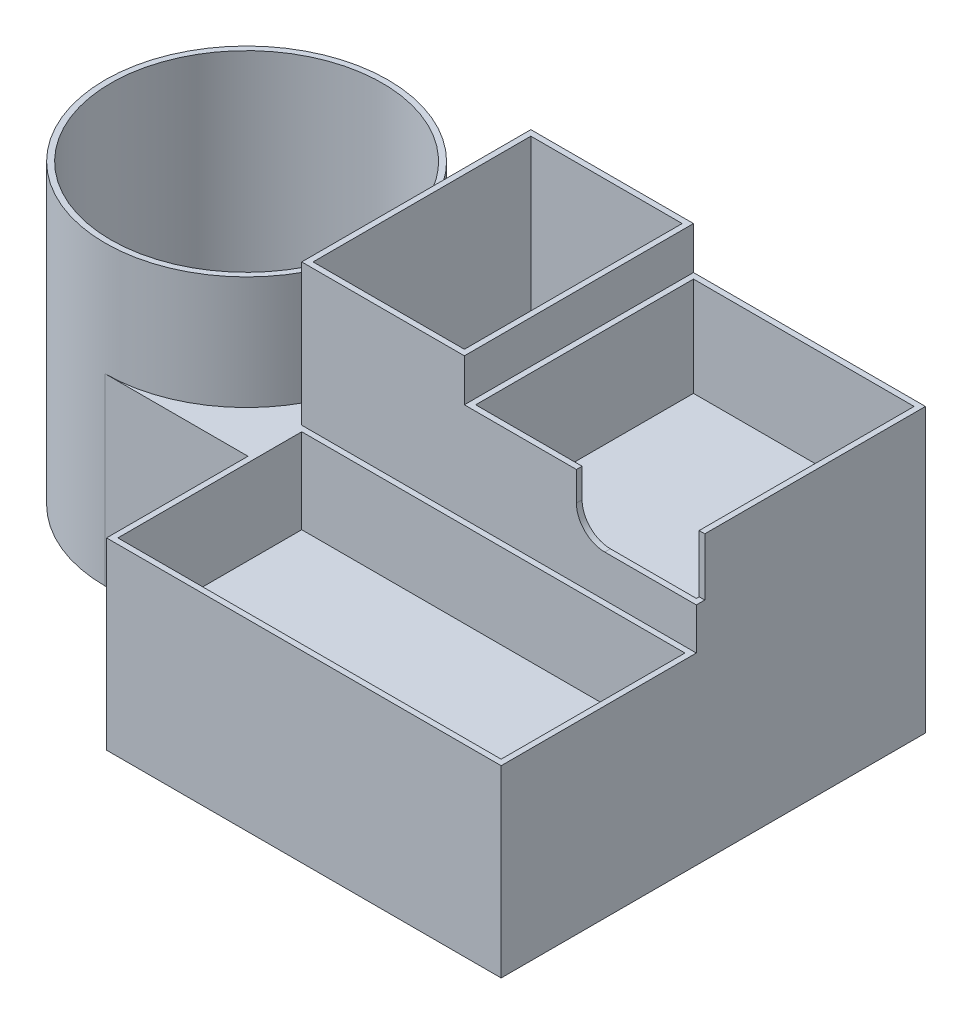
SolidWorks part; units mm, degrees
ref_plane "Front Plane" through (0, 0, 0) normal (0, 0, 1) x (1, 0, 0)
ref_plane "Top Plane" through (0, 0, 0) normal (0, 1, 0) x (1, 0, 0)
ref_plane "Right Plane" through (0, 0, 0) normal (1, 0, 0) x (0, 0, -1)
sketch "Sketch1" plane through (0, 0, 0) normal (0, 1, 0) x (1, 0, 0)
  line L1 (-70, -50) -> (120, -50)
  line L2 (-120, 0) -> (-120, 1)
  line L3 (-71, 50) -> (120, 50)
  line L4 (120, -50) -> (120, 50)
  line L5 (-120, -50) -> (120, 50) construction
  line L6 (-120, 50) -> (120, -50) construction
  arc A0 (-70, -50) -> (-120, 0) centre (-70, 0) cw
  arc A1 (-71, 50) -> (-120, 1) centre (-71, 1) ccw
  point P0 (0, 0)
  dimension "D3" = 50
  dimension "D4" = 49
  dimension "D1" = 240
  dimension "D2" = 100
extrude "Boss-Extrude1" add sketch "Sketch1" along normal blind 65
sketch "Sketch2" plane through (0, 65, 0) normal (0, 1, 0) x (1, 0, 0)
  line L1 (120, 50) -> (38, 50)
  line L2 (120, 50) -> (120, -31)
  line L3 (120, -31) -> (38, -31)
  line L4 (38, 50) -> (38, -31)
  line L5 (38, 50) -> (-19.5, 50)
  line L6 (38, 50) -> (38, -31)
  line L7 (38, -31) -> (-19.5, -31)
  line L8 (-19.5, 50) -> (-19.5, -31)
  line L9 (-17.5, 48) -> (36, 48)
  line L10 (-17.5, 48) -> (-17.5, -29)
  line L11 (-17.5, -29) -> (36, -29)
  line L12 (36, 48) -> (36, -29)
  line L13 (40, 48) -> (118, 48)
  line L14 (40, 48) -> (40, -29)
  line L15 (40, -29) -> (118, -29)
  line L16 (118, 48) -> (118, -29)
  circle A0 centre (-70, 0) radius 50
  circle A1 centre (-70, 0) radius 48
  point P19 (115.6052, -26.5015)
  line M10 (120, -50) -> (120, 50)
  line M11 (120, 50) -> (-71, 50)
  arc M15 (-120, 0) -> (-70, -50) centre (-70, 0) ccw
  dimension "D1" = 100
  dimension "D6" = 2
  dimension "D2" = 82
  dimension "D3" = 81
  dimension "D4" = 57.5
  dimension "D5" = 70
  dimension "D7" = 2
  dimension "D8" = 2
  dimension "D9" = 2
  dimension "D10" = 2
  dimension "D11" = 2
  dimension "D12" = 2
  dimension "D13" = 2
  dimension "D14" = 2
extrude "Boss-Extrude3" add sketch "Sketch2" along normal blind 100 from offset 60 contours A0 M15 region at (-35.6447, 65, 34.3553) offset against normal yes
extrude "Cut-Extrude1" cut sketch "Sketch2<6>" against normal blind 50 contours A1 region at (-70, 65, 0)
sketch "Sketch2<6>" plane through (0, 65, 0) normal (0, 1, 0) x (1, 0, 0) same geometry as "Sketch2"
extrude "Boss-Extrude6" add sketch "Sketch2<9>" along normal blind 100 from offset 50 contours L8 L7 L4 M11 region at (37.0067, 65, -9.5) offset against normal yes
sketch "Sketch2<9>" plane through (0, 65, 0) normal (0, 1, 0) x (1, 0, 0) same geometry as "Sketch2"
extrude "Cut-Extrude2" cut sketch "Sketch2<10>" against normal blind 50 contours L12 L9 L10 L11 region at (9.25, 65, -9.5)
sketch "Sketch2<10>" plane through (0, 65, 0) normal (0, 1, 0) x (1, 0, 0) same geometry as "Sketch2"
extrude "Boss-Extrude7" add sketch "Sketch2<11>" along normal blind 35 contours L4 L3 M11 M10 region at (118.8474, 65, -9.5)
sketch "Sketch2<11>" plane through (0, 65, 0) normal (0, 1, 0) x (1, 0, 0) same geometry as "Sketch2"
sketch "Sketch5" plane through (0, 0, 31) normal (0, 0, 1) x (1, 0, 0)
  line L0 (77.6115, 100) -> (77.6115, 89.7255)
  line L1 (120, 100) -> (38, 100) construction
  line L2 (87.6115, 79.7255) -> (120, 79.7255)
  line L3 (120, 100) -> (120, 65) construction
  line L4 (77.6115, 100) -> (120, 100)
  line L5 (120, 100) -> (120, 79.7255)
  arc A0 (87.6115, 79.7255) -> (77.6115, 89.7255) centre (87.6115, 89.7255) cw
  dimension "D1" = 10
extrude "Cut-Extrude4" cut sketch "Sketch5" against normal blind 3
sketch "Sketch10" plane through (0, 65, 0) normal (0, 1, 0) x (1, 0, 0)
  line L0 (-19.5, -31) -> (-19.5, 50) construction
  line L1 (120, -50) -> (-19.5, -50)
  line L2 (120, -50) -> (120, -100)
  line L3 (120, -100) -> (-19.5, -100)
  line L4 (-19.5, -50) -> (-19.5, -100)
  dimension "D1" = 50
extrude "Boss-Extrude9" add sketch "Sketch10" against normal blind 65
extrude "Cut-Extrude5" cut sketch "Sketch10<3>" against normal blind 20
sketch "Sketch10<3>" plane through (0, 65, 0) normal (0, 1, 0) x (1, 0, 0) same geometry as "Sketch10"
sketch "Sketch7" plane through (0, 65, 0) normal (0, 1, 0) x (1, 0, 0)
  line L0 (-19.5, -50) -> (-19.5, -100)
  line L1 (-70, -50) -> (120, -50) construction
  line L2 (-19.5, -100) -> (120, -100)
  line L3 (120, -100) -> (120, -50)
  line L9 (120, -50) -> (120, -31)
  line L10 (120, -31) -> (-19.5, -31)
  line L11 (-19.5, -31) -> (-19.5, 50)
  line L12 (-19.5, 50) -> (-70, 50)
  line L13 (-70, -50) -> (120, -50)
  line L18 (-19.5, -50) -> (120, -50)
  arc A1 (-70, -50) -> (-70, 50) centre (-70, 0) ccw
  dimension "D1" = 50
  dimension "D2" = 0
extrude "Boss-Extrude8" add sketch "Sketch7" against normal blind 65
sketch "Sketch8" plane through (0, 65, 0) normal (0, 1, 0) x (1, 0, 0)
  line L0 (-19.5, -50) -> (-19.5, -100) construction
  line L1 (-17.5, -98) -> (118, -98)
  line L2 (-17.5, -98) -> (-17.5, -33)
  line L3 (-17.5, -33) -> (118, -33)
  line L4 (118, -98) -> (118, -33)
  line L5 (-19.5, -100) -> (120, -100) construction
  line L6 (120, -100) -> (120, -31) construction
  line L7 (38, -31) -> (-19.5, -31) construction
  dimension "D1" = 2
  dimension "D2" = 2
  dimension "D3" = 2
  dimension "D4" = 2
extrude "Cut-Extrude6" cut sketch "Sketch8" against normal blind 30
